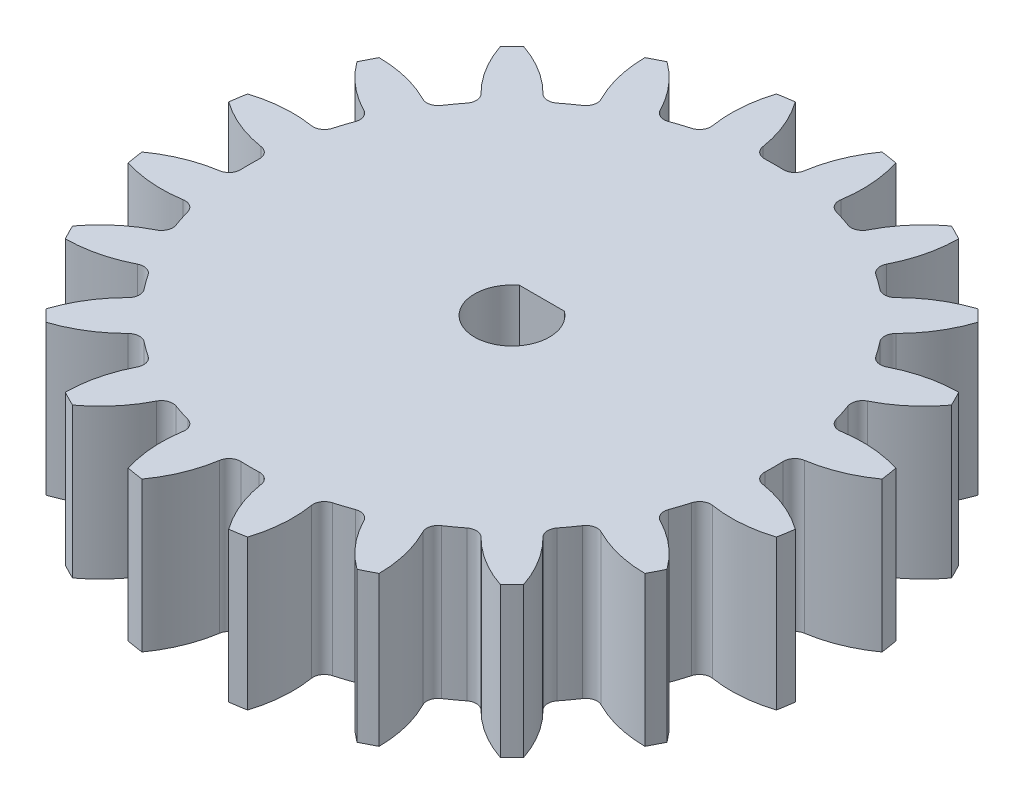
SolidWorks part; units mm, degrees
ref_plane "Front Plane" through (0, 0, 0) normal (0, 0, 1) x (1, 0, 0)
ref_plane "Top Plane" through (0, 0, 0) normal (0, 1, 0) x (1, 0, 0)
ref_plane "Right Plane" through (0, 0, 0) normal (1, 0, 0) x (0, 0, -1)
sketch "Sketch1" plane through (0, 0, 0) normal (0, 1, 0) x (1, 0, 0)
  circle A0 centre (0, 0) radius 2.5
  circle A1 centre (0, 0) radius 22
  dimension "D1" = 5
  dimension "D2" = 44
extrude "Boss-Extrude1" add sketch "Sketch1" along normal blind 10
sketch "Sketch2" plane through (0, 10, 0) normal (0, 1, 0) x (1, 0, 0)
  line L0 (0, 0) -> (0, 22) construction
  line L1 (-1.3103, 17.4509) -> (0, 0) construction
  line L2 (0, 14.786) -> (-2.5708, 21.8493) construction
  circle A0 centre (0, 0) radius 22 construction
  arc A1 (1.3103, 17.4509) -> (-1.3103, 17.4509) centre (0, 0) ccw
  arc A2 (1.8681, 19.9126) -> (-1.8681, 19.9126) centre (0, 0) ccw construction
  arc A3 (2.8963, 21.8085) -> (-2.8963, 21.8085) centre (0, 0) ccw
  arc A4 (-2.8963, 21.8085) -> (-1.3103, 17.4509) centre (-9.8515, 16.8096) cw
  arc A5 (2.8963, 21.8085) -> (1.3103, 17.4509) centre (9.8515, 16.8096) ccw
  point P16 (-1.8028, 19.7391)
  dimension "D1" = 44
  dimension "D2" = 40
  dimension "D3" = 4.5
  dimension "D4" = 20
  dimension "D5" = 3.7416
extrude "Cut-Extrude1" cut sketch "Sketch2" against normal through all
fillet "Fillet1" radius 0.76 2 edges at (1.3103, 5, -17.4509) (-1.3103, 5, -17.4509)
pattern_circular "CirPattern2" count 20 over 360 about axis through (0, 10, 0) along (0, 1, 0) of "Cut-Extrude1", "Fillet1"
sketch "Sketch3" plane through (0, 10, 0) normal (0, 1, 0) x (1, 0, 0)
  circle A0 centre (0, 0) radius 20 construction
  dimension "D1" = 40
sketch "Sketch4" plane through (0, 0, 0) normal (0, 1, 0) x (1, 0, 0)
  line L0 (-1.5, 2) -> (1.5, 2)
  arc A0 (1.5, 2) -> (-1.5, 2) centre (0, 0) ccw
  dimension "D2" = 2.5
  dimension "D1" = 2
extrude "Boss-Extrude2" add sketch "Sketch4" along normal blind 10
equation "\"Module\"= 2"
equation "\"No. of Teeth\"= 20"
equation "\"Bore Diameter\"= 5"
equation "\"Pressure Angle\"= 20deg"
equation "\"Outer Diameter\"= ( \"No. of Teeth\" + 2 ) * \"Module\""
equation "\"Pitch Diameter\"= \"No. of Teeth\" * \"Module\""
equation "\"Backlash\"= 0.3 * \"Module\""
equation "\"Arc Length\"= ( \"Module\" * pi ) / 2 + \"Backlash\""
equation "\"Fillet Radius\"= .38 * \"Module\""
equation "\"Tooth Depth\"= IIF ( \"Module\" <= 1.25 , 2.4 * \"Module\" , 2.25 * \"Module\" )"
equation "\"D1@Sketch1\"=\"Bore Diameter\""
equation "\"D2@Sketch1\"=\"Outer Diameter\""
equation "\"D2@Sketch2\"=\"Pitch Diameter\""
equation "\"D1@Sketch2\"=\"Outer Diameter\""
equation "\"D3@Sketch2\"=\"Tooth Depth\""
equation "\"D4@Sketch2\"=\"Pressure Angle\""
equation "\"D5@Sketch2\"=\"Arc Length\""
equation "\"D1@Fillet1\"=\"Fillet Radius\""
equation "\"D1@CirPattern2\"=\"No. of Teeth\""
equation "\"D1@Sketch3\"=\"Pitch Diameter\""
